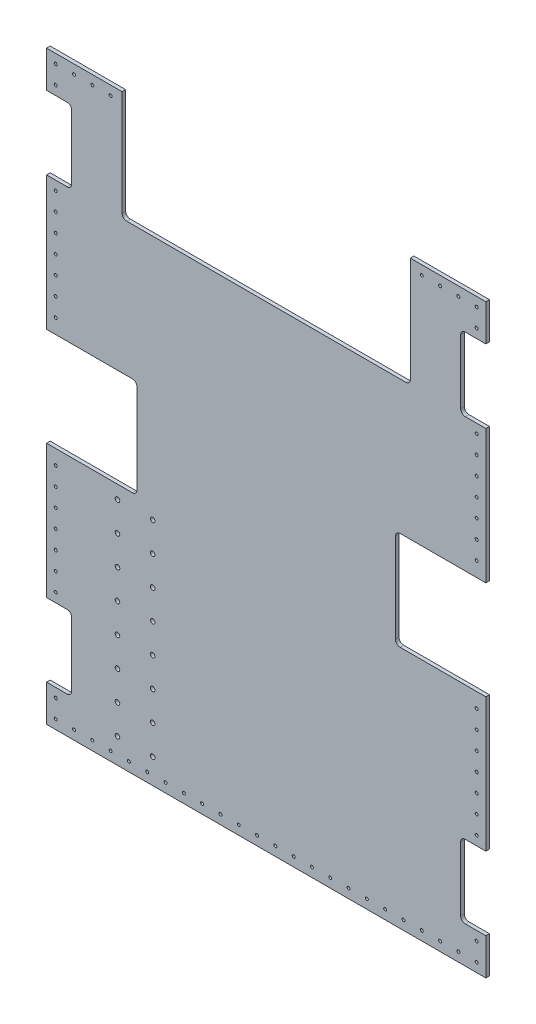
SolidWorks part; units mm, degrees
material "Beech"
ref_plane "Front Plane" through (0, 0, 0) normal (0, 0, 1) x (1, 0, 0)
ref_plane "Top Plane" through (0, 0, 0) normal (0, 1, 0) x (1, 0, 0)
ref_plane "Right Plane" through (0, 0, 0) normal (1, 0, 0) x (0, 0, -1)
sketch "Sketch1" plane through (0, 0, 0) normal (0, 0, 1) x (1, 0, 0)
  line L0 (-631.825, -406.4) -> (73.025, -406.4) construction
  line L8 (-552.45, -292.9527) -> (-552.45, -297.5164) construction
  line L9 (-584.2, -355.6) -> (-549.275, -355.6)
  line L10 (-584.2, -355.6) -> (-584.2, -254)
  line L11 (-584.2, -254) -> (-549.275, -254)
  line L12 (-549.275, -355.6) -> (-549.275, -254)
  line L13 (-571.5, -368.3) -> (-571.5, -342.9) construction
  line L14 (-571.5, -266.7) -> (-571.5, -241.3) construction
  line L15 (-279.4, -419.1) -> (-279.4, 419.1) construction
  line L16 (25.4, -406.4) -> (25.4, 406.4)
  line L17 (25.4, -254) -> (-9.525, -254)
  line L18 (-9.525, -355.6) -> (-9.525, -254)
  line L19 (25.4, -355.6) -> (-9.525, -355.6)
  line L20 (25.4, 0) -> (-584.2, 0) construction
  line L21 (25.4, 254) -> (-9.525, 254)
  line L22 (-9.525, 355.6) -> (-9.525, 254)
  line L23 (25.4, 355.6) -> (-9.525, 355.6)
  line L24 (-584.2, 254) -> (-549.275, 254)
  line L25 (-584.2, 355.6) -> (-549.275, 355.6)
  line L26 (-549.275, 355.6) -> (-549.275, 254)
  line L27 (-477.8375, -68.4315) -> (-471.4875, -68.4315) construction
  line L28 (-584.2, 68.4315) -> (-458.7875, 68.4315)
  line L29 (-584.2, 68.4315) -> (-584.2, -68.4315)
  line L30 (-584.2, -68.4315) -> (-458.7875, -68.4315)
  line L32 (-477.8375, 68.4315) -> (-471.4875, 68.4315) construction
  line L33 (25.4, 68.4315) -> (-100.0125, 68.4315)
  line L34 (25.4, -68.4315) -> (-100.0125, -68.4315)
  line L35 (-100.0125, 68.4315) -> (-100.0125, -68.4315)
  line L37 (-79.375, 406.4) -> (-479.425, 406.4)
  line L38 (-79.375, 406.4) -> (-79.375, 254)
  line L39 (-79.375, 254) -> (-479.425, 254)
  line L40 (-479.425, 406.4) -> (-479.425, 254)
  line L42 (-458.7875, -68.4315) -> (-458.7875, 68.4315)
  line L43 (-471.4875, -20.8772) -> (-471.4875, 20.8772) construction
  line L44 (-584.2, -406.4) -> (-584.2, 406.4)
  line L46 (-584.2, -381) -> (-584.2, 381) construction
  line L47 (25.4, -381) -> (25.4, 381) construction
  line L48 (-79.375, 406.4) -> (25.4, 406.4)
  line L49 (-479.425, 406.4) -> (-584.2, 406.4)
  line L50 (25.4, -406.4) -> (-584.2, -406.4)
  line L51 (-479.425, 406.4) -> (-479.425, 381) construction
  point P22 (-571.5, -355.6)
  point P27 (-571.5, -254)
  dimension "D1" = 3.175
  dimension "D2" = 12.7
  dimension "D3" = 152.4
extrude "Boss-Extrude1" add sketch "Sketch1" along normal blind 5 contours L40 L25 L26 L24 L28 L42 L30 L11 L12 L9 L19 L18 L17 L16 L34 L35 L33 L21 L22 L23 L38 L39 region at (-279.4, -52.1551, 0)
sketch "Sketch4" plane through (0, 0, 5) normal (0, 0, 1) x (1, 0, 0)
  circle A1 centre (-571.5, 393.7) radius 2.0701 construction
  circle A2 centre (-571.5, 393.7) radius 2.0701
extrude "Cut-Extrude1" cut sketch "Sketch4" against normal through all both and the other way through all
pattern_linear "LPattern2" count 24 spacing 25.4 along (1, 0, 0) skipping (4, 0), (5, 0), (6, 0), (7, 0), (8, 0), (9, 0), (10, 0), (11, 0), (12, 0), (13, 0), (14, 0), (15, 0), (16, 0), (17, 0), (18, 0), (19, 0) of "Cut-Extrude1"
pattern_linear "LPattern3" count 32 spacing 25.4 along (0, -1, 0) skipping (2, 0), (3, 0), (4, 0), (5, 0), (14, 0), (15, 0), (16, 0), (17, 0), (18, 0), (26, 0), (27, 0), (28, 0), (29, 0) of "Cut-Extrude1"
pattern_linear "LPattern4" count 24 spacing 25.4 along (1, 0, 0) of face at (-569.4299, -393.7, 5)
pattern_linear "LPattern5" count 31 spacing 25.4 along (0, -1, 0) skipping (2, 0), (3, 0), (4, 0), (5, 0), (13, 0), (14, 0), (15, 0), (16, 0), (17, 0), (18, 0), (26, 0), (27, 0), (28, 0), (29, 0) of face at (14.7701, 393.7, 5)
fillet "Fillet1" radius 6.35 14 edges at (-9.525, 355.6, 2.5) (-9.525, 254, 2.5) (-100.0125, -68.4315, 2.5) (-100.0125, 68.4315, 2.5) (-9.525, -355.6, 2.5) (-9.525, -254, 2.5) (-549.275, -355.6, 2.5) (-549.275, -254, 2.5) (-458.7875, -68.4315, 2.5) (-458.7875, 68.4315, 2.5) (-549.275, 355.6, 2.5) (-549.275, 254, 2.5) (-479.425, 254, 2.5) (-79.375, 254, 2.5)
sketch "Sketch6" plane through (0, 0, 0) normal (0, 0, -1) x (-1, 0, 0)
  line L1 (436.9527, -334.01) -> (485.7877, -334.01)
  line L2 (436.9527, -334.01) -> (436.9527, -368.3)
  line L3 (436.9527, -368.3) -> (485.7877, -368.3)
  line L4 (485.7877, -334.01) -> (485.7877, -368.3)
  line L6 (631.825, -381) -> (-73.025, -381) construction
  line L8 (498.4877, -308.9728) -> (498.4877, -299.8194) construction
  circle A0 centre (436.9527, -330.835) radius 3.175
  circle A1 centre (436.9527, -371.475) radius 3.175
  circle A2 centre (485.7877, -371.475) radius 3.175
  circle A3 centre (485.7877, -330.835) radius 3.175
  circle A4 centre (436.9527, -351.155) radius 0.0127
  dimension "D1" = 6.35
  dimension "D5" = 12.7
  dimension "D6" = 0.0254
  dimension "D2" = 40.64
  dimension "D3" = 48.835
  dimension "D4" = 12.7
extrude "Cut-Extrude2" cut sketch "Sketch6" against normal through all contours A0 | A1 | A2 | A3 | L2 A4 | L2 A4 region at (-485.7877, -330.835, 0) region at (-485.7877, -371.475, 0) region at (-436.9527, -371.475, 0) region at (-436.9527, -330.835, 0) region at (-436.9581, -351.155, 0) region at (-436.9473, -351.155, 0)
pattern_linear "LPattern6" count 7 spacing 40.64 along (0, 1, 0) of "Cut-Extrude2"
